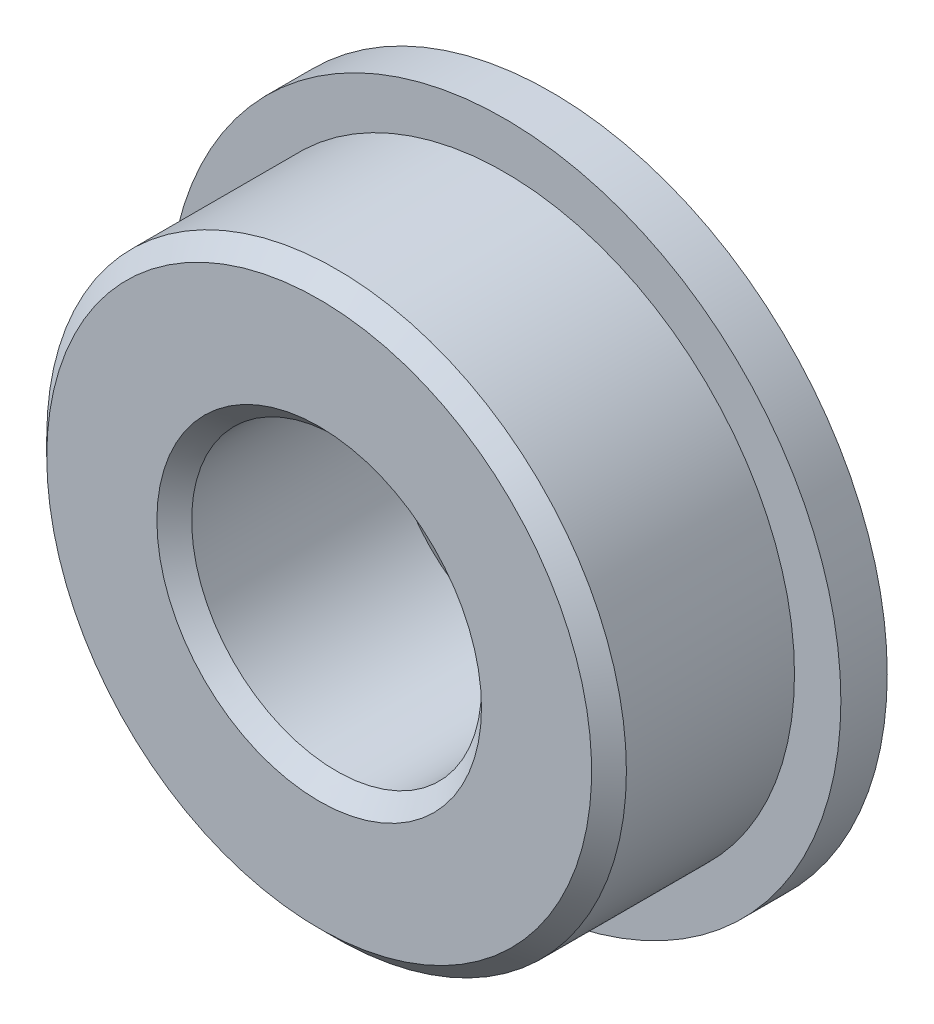
SolidWorks part; units mm, degrees
ref_plane "Front Plane" through (0, 0, 0) normal (0, 0, 1) x (1, 0, 0)
ref_plane "Top Plane" through (0, 0, 0) normal (0, 1, 0) x (1, 0, 0)
ref_plane "Right Plane" through (0, 0, 0) normal (1, 0, 0) x (0, 0, -1)
sketch "Sketch1" plane through (0, 0, 0) normal (1, 0, 0) x (0, 0, -1)
  line L0 (0, 0) -> (3.1741, 0) construction
  line L1 (0, 2.5) -> (0, 0) construction
  line L2 (-2, 2.5) -> (2, 2.5)
  line L3 (-2, 2.5) -> (-2, 5)
  line L4 (1.2, 5.8) -> (2, 5.8)
  line L5 (2, 2.5) -> (2, 5.8)
  line L6 (1.2, 5) -> (-2, 5)
  line L7 (1.2, 5) -> (1.2, 5.8)
  dimension "D1" = 2.5
  dimension "D2" = 5
  dimension "D3" = 4
  dimension "D4" = 0.8
  dimension "D5" = 5.8
revolve "Revolve1" add sketch "Sketch1" angle 360 about L0
chamfer "Chamfer1" distance 0.3 angle 45 3 edges at (2.5, 0, -2) (2.5, 0, 2) (5, 0, 2)
